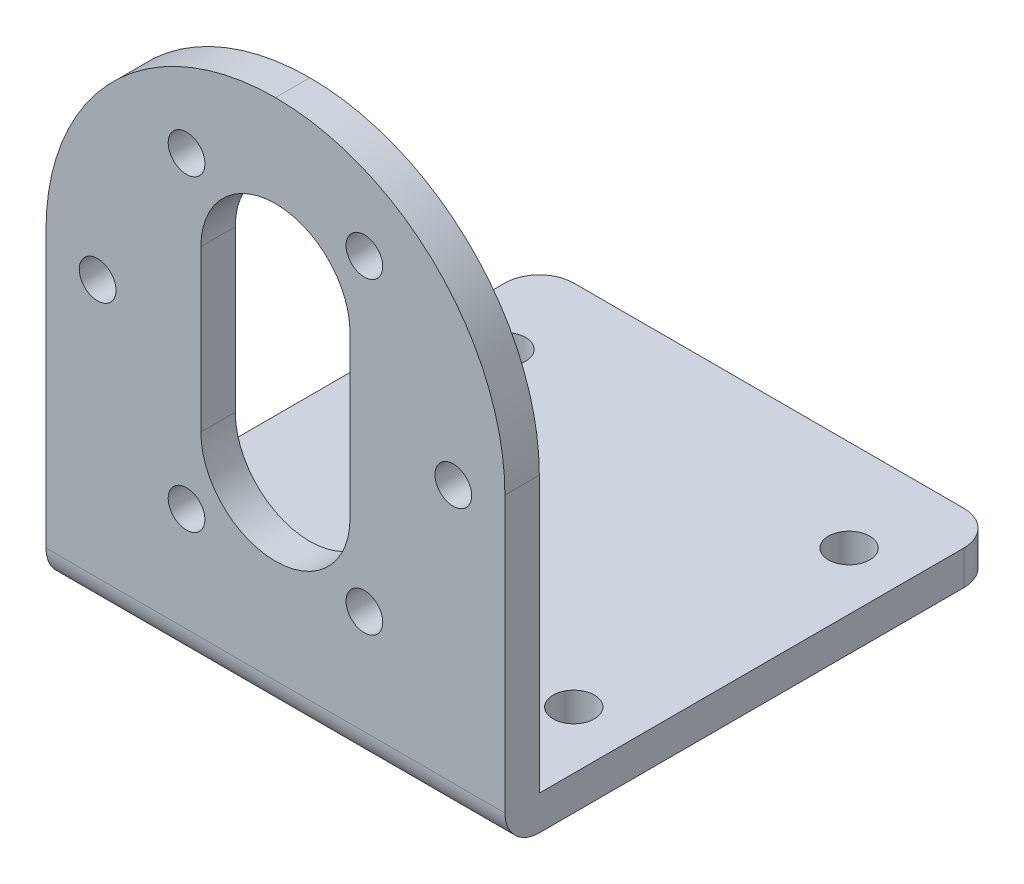
SolidWorks part; units mm, degrees
ref_plane "前视基准面" through (0, 0, 0) normal (0, 0, 1) x (1, 0, 0)
ref_plane "上视基准面" through (0, 0, 0) normal (0, 1, 0) x (1, 0, 0)
ref_plane "右视基准面" through (0, 0, 0) normal (1, 0, 0) x (0, 0, -1)
sketch "草图1" plane through (0, 0, 0) normal (0, 1, 0) x (1, 0, 0)
  line L1 (-20, 21.5) -> (20, 21.5)
  line L2 (-20, 21.5) -> (-20, -21.5)
  line L3 (-20, -21.5) -> (20, -21.5)
  line L4 (20, 21.5) -> (20, -21.5)
  circle A0 centre (-15, 13.5) radius 1.8
  circle A1 centre (15, 13.5) radius 1.8
  circle A2 centre (15, -10.5) radius 1.8
  circle A3 centre (-15, -10.5) radius 1.8
  dimension "D5" = 3.6
  dimension "D1" = 43
  dimension "D2" = 40
  dimension "D3" = 20
  dimension "D4" = 21.5
  dimension "D6" = 5
  dimension "D7" = 8
  dimension "D8" = 2
  dimension "D9" = 2
extrude "凸台-拉伸1" add sketch "草图1" along normal blind 3
sketch "草图2" plane through (0, 3, 0) normal (0, 1, 0) x (1, 0, 0)
  line L0 (-20, 21.5) -> (-20, -21.5) construction
  line L1 (-20, -18.5) -> (20, -18.5)
  line L2 (-20, -18.5) -> (-20, -21.5)
  line L3 (-20, -21.5) -> (20, -21.5)
  line L4 (20, -18.5) -> (20, -21.5)
  dimension "D1" = 3
extrude "凸台-拉伸2" add sketch "草图2" along normal blind 44
sketch "草图3" plane through (0, 0, 18.5) normal (0, 0, -1) x (-1, 0, 0)
  line L0 (0, 32.5) -> (0, 18.5) construction
  line L1 (6.5, 32.5) -> (6.5, 18.5)
  line L2 (-6.5, 32.5) -> (-6.5, 18.5)
  line L3 (-20, 0) -> (20, 0) construction
  line L4 (20, 25.5) -> (-20, 25.5) construction
  line L5 (0, 47) -> (0, 3) construction
  line L6 (-20, 47) -> (20, 47) construction
  line L7 (-20, 3) -> (20, 3) construction
  line L8 (20, 47) -> (20, 3) construction
  line L9 (-20, 47) -> (-20, 3) construction
  line L10 (-7.75, 38.9234) -> (0, 25.5) construction
  line L11 (-7.75, 12.0766) -> (0, 25.5) construction
  arc A0 (6.5, 32.5) -> (-6.5, 32.5) centre (0, 32.5) ccw
  arc A1 (-6.5, 18.5) -> (6.5, 18.5) centre (0, 18.5) ccw
  circle A2 centre (15.5, 25.5) radius 1.6
  circle A3 centre (0, 25.5) radius 15.5 construction
  circle A4 centre (-15.5, 25.5) radius 1.6
  circle A5 centre (-7.75, 38.9234) radius 1.6
  circle A6 centre (-7.75, 12.0766) radius 1.6
  circle A7 centre (7.75, 12.0766) radius 1.6
  circle A8 centre (7.75, 38.9234) radius 1.6
  point P3 (0, 25.5)
  dimension "D4" = 3.2
  dimension "D5" = 31
  dimension "D8" = 3.2
  dimension "D9" = 3.2
  dimension "D1" = 14
  dimension "D2" = 32.5
  dimension "D3" = 13
  dimension "D6" = 60
  dimension "D7" = 60
extrude "切除-拉伸1" cut sketch "草图3" against normal blind 44
fillet "圆角1" radius 20 2 edges at (-20, 47, 20) (20, 47, 20)
fillet "圆角2" radius 3 1 edges at (20, 1.5, -21.5)
fillet "圆角3" radius 3 1 edges at (-20, 1.5, -21.5)
fillet "圆角4" radius 3 1 edges at (0, 0, 21.5)
